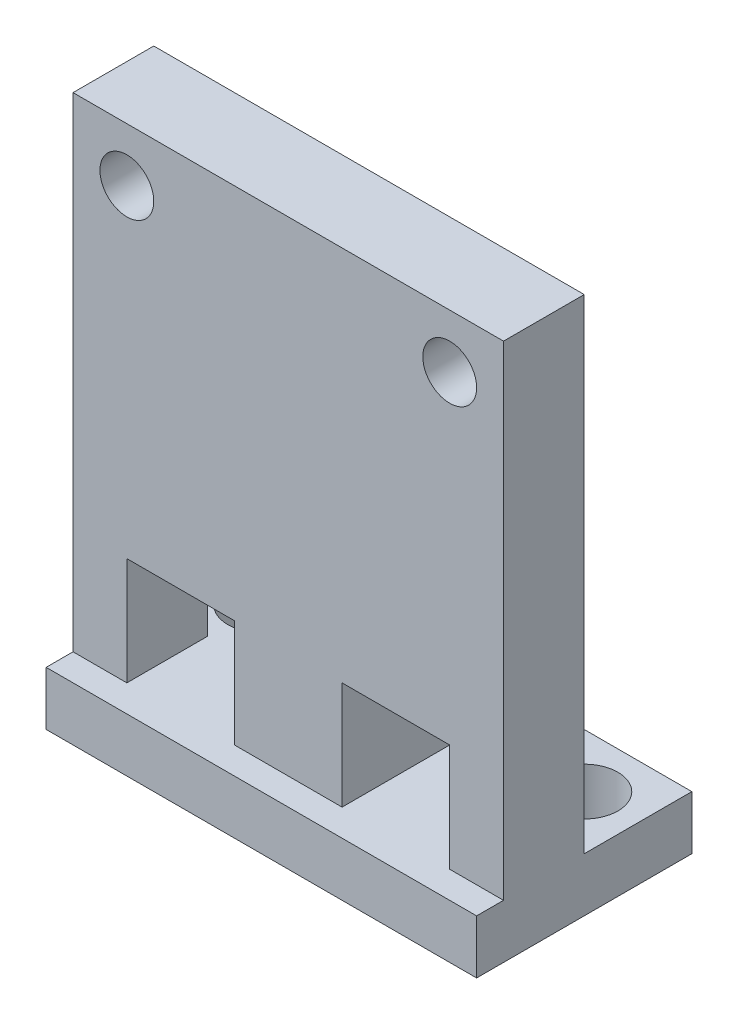
SolidWorks part; units mm, degrees
ref_plane "Front Plane" through (0, 0, 0) normal (0, 0, 1) x (1, 0, 0)
ref_plane "Top Plane" through (0, 0, 0) normal (0, 1, 0) x (1, 0, 0)
ref_plane "Right Plane" through (0, 0, 0) normal (1, 0, 0) x (0, 0, -1)
sketch "Sketch1" plane through (0, 0, 0) normal (0, 0, 1) x (1, 0, 0)
  line L1 (0, 0) -> (20.32, 0)
  line L2 (0, 0) -> (0, 25.4)
  line L3 (0, 25.4) -> (20.32, 25.4)
  line L4 (20.32, 0) -> (20.32, 25.4)
  dimension "D1" = 20.32
  dimension "D2" = 25.4
extrude "Boss-Extrude1" add sketch "Sketch1" along normal blind 5.08
sketch "Sketch2" plane through (0, 0, 5.08) normal (0, 0, 1) x (1, 0, 0)
  line L1 (0, 25.4) -> (0, 0) construction
  line L2 (20.32, 25.4) -> (0, 25.4) construction
  circle A0 centre (2.54, 22.86) radius 1.27
  circle A1 centre (17.78, 22.86) radius 1.27
  point P4 (0, 0)
  dimension "D4" = 2.54
  dimension "D1" = 15.24
  dimension "D2" = 2.54
  dimension "D3" = 2.54
extrude "Cut-Extrude1" cut sketch "Sketch2" against normal up to next
sketch "Sketch3" plane through (0, 0, 0) normal (0, -1, 0) x (1, 0, 0)
  line L0 (20.32, 5.08) -> (20.32, 0) construction
  line L1 (0, 5.08) -> (20.32, 5.08)
  line L2 (0, 5.08) -> (0, -5.08)
  line L3 (0, -5.08) -> (20.32, -5.08)
  line L4 (20.32, 5.08) -> (20.32, -5.08)
  dimension "D1" = 10.16
extrude "Boss-Extrude2" add sketch "Sketch3" against normal blind 2.54
sketch "Sketch4" plane through (0, 0, 5.08) normal (0, 0, 1) x (1, 0, 0)
  line L0 (0, 25.4) -> (0, 0) construction
  line L1 (20.32, 25.4) -> (0, 25.4)
  line L2 (20.32, 25.4) -> (20.32, 2.54)
  line L3 (20.32, 2.54) -> (0, 2.54)
  line L4 (0, 25.4) -> (0, 2.54)
  line L5 (0, 0) -> (20.32, 0) construction
  dimension "D1" = 2.54
extrude "Cut-Extrude2" cut sketch "Sketch4" against normal blind 1.27
sketch "Sketch5" plane through (0, 2.54, 0) normal (0, 1, 0) x (1, 0, 0)
  line L0 (20.32, 5.08) -> (20.32, 0) construction
  line L1 (0, 0) -> (0, 5.08) construction
  line L2 (20.32, 0) -> (0, 0) construction
  circle A0 centre (17.78, 2.54) radius 1.5875
  circle A1 centre (2.54, 2.54) radius 1.5875
  point P4 (0, 0)
  dimension "D1" = 3.175
  dimension "D2" = 2.54
  dimension "D3" = 2.54
  dimension "D4" = 2.54
extrude "Cut-Extrude3" cut sketch "Sketch5" against normal blind 2.54
sketch "Sketch6" plane through (0, 0, 3.81) normal (0, 0, 1) x (1, 0, 0)
  line L0 (0, 2.54) -> (20.32, 2.54) construction
  line L1 (2.54, 2.54) -> (17.78, 2.54)
  line L2 (2.54, 2.54) -> (2.54, 7.62)
  line L3 (2.54, 7.62) -> (17.78, 7.62)
  line L4 (17.78, 2.54) -> (17.78, 7.62)
  line L5 (0, 25.4) -> (0, 2.54) construction
  point P6 (0, 0)
  dimension "D1" = 15.24
  dimension "D2" = 5.08
  dimension "D3" = 2.54
extrude "Cut-Extrude4" cut sketch "Sketch6" against normal through all
ref_plane "Plane1" through (10.16, 0, 0) normal (-1, 0, 0) x (0, 0, 1)
sketch "Sketch7" plane through (10.16, 0, 0) normal (-1, 0, 0) x (0, 0, 1)
  line L0 (0, 25.4) -> (-5.08, 2.54)
  line L3 (-5.08, 2.54) -> (3.81, 2.54)
  line L4 (3.81, 2.54) -> (3.81, 25.4)
  line L5 (3.81, 25.4) -> (0, 25.4)
extrude "Boss-Extrude3" add sketch "Sketch7" along normal blind 2.54
mirror "Mirror1" about plane through (10.16, 0, 0) normal (-1, 0, 0) of "Boss-Extrude3"
